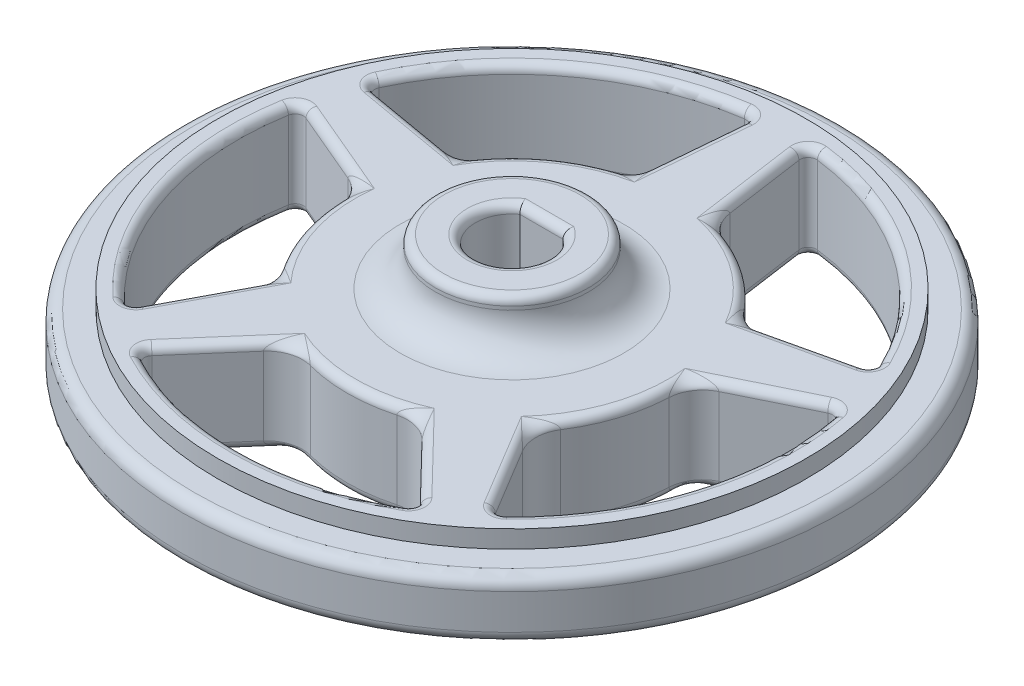
SolidWorks part; units mm, degrees
ref_plane "Front Plane" through (0, 0, 0) normal (0, 0, 1) x (1, 0, 0)
ref_plane "Top Plane" through (0, 0, 0) normal (0, 1, 0) x (1, 0, 0)
ref_plane "Right Plane" through (0, 0, 0) normal (1, 0, 0) x (0, 0, -1)
sketch "Croquis1" plane through (0, 0, 0) normal (0, 1, 0) x (1, 0, 0)
  circle A0 centre (0, 0) radius 6.5
  dimension "D1" = 13
sketch "Sketch1" plane through (0, 0, 0) normal (0, 1, 0) x (1, 0, 0)
  line L0 (4, 0) -> (-4, 0) construction
  line L1 (-3.2894, 13.6081) -> (-2.4528, 23.1705)
  line L2 (0, 0) -> (0, 7.6318) construction
  line L3 (3.2894, 13.6081) -> (1.9176, 23.221)
  line L4 (11.9255, 7.3336) -> (21.2785, 9.4929)
  line L5 (13.9585, 1.0767) -> (22.677, 5.3519)
  line L6 (10.6598, -9.0757) -> (15.6037, -17.3036)
  line L7 (5.3374, -12.9426) -> (12.0976, -19.9133)
  line L8 (-5.3374, -12.9426) -> (-11.6349, -20.1871)
  line L9 (-10.6598, -9.0757) -> (-15.2003, -17.659)
  line L10 (-13.9585, 1.0767) -> (-22.7945, 4.8273)
  line L11 (-11.9255, 7.3336) -> (-21.4919, 8.9994)
  circle A0 centre (0, 0) radius 28
  circle A1 centre (0, 0) radius 25
  circle A2 centre (0, 0) radius 23.3
  circle A3 centre (0, 0) radius 14
  point P11 (0, 0)
  point P34 (0, 0)
  dimension "D1" = 56
  dimension "D4" = 28
  dimension "D5" = 85
  dimension "D6" = 8
  dimension "D2" = 3
  dimension "D3" = 4.7
  dimension "D7" = 5
extrude "Boss-Extrude1" add sketch "Sketch1" along normal mid plane 8 contours A1 A2 region at (-24.2929, 0, 0)
extrude "Boss-Extrude2" add sketch "Sketch1<3>" along normal mid plane 8 contours A3 L11 A2 L10 | A3 | A3 L3 A2 L1 | A3 L5 A2 L4 | A3 L7 A2 L6 | A3 L9 A2 L8 region at (-0.1269, 0, -18.2557) region at (0, 0, 0) region at (-17.4015, 0, -5.5206) region at (17.323, 0, -5.762) region at (-10.6278, 0, 14.8438) region at (10.8331, 0, 14.6946)
sketch "Sketch1<3>" plane through (0, 0, 0) normal (0, 1, 0) x (1, 0, 0) same geometry as "Sketch1"
extrude "Saliente-Extruir1" add sketch "Croquis1" along normal blind 8
sketch "Sketch3" plane through (0, 4, 0) normal (0, 1, 0) x (1, 0, 0)
  line L0 (3.609, -2) -> (-3.609, -2) construction
  line L1 (3.609, 12) -> (-3.609, 12) construction
  line L2 (-1.833, 2.5) -> (1.833, 2.5)
  arc A4 (-1.833, 2.5) -> (1.833, 2.5) centre (0, 0) ccw
  point P8 (0, -2)
  point P11 (0, 12)
  point P17 (0, 0)
  dimension "D1" = 2.5
  dimension "D5" = 6.2
  dimension "D3" = 14
extrude "Cortar-Extruir1" cut sketch "Sketch3" against normal through all both and the other way through all
fillet "Fillet1" radius 0.7 55 edges at (13.1318, -4, 13.1896) (8.7175, -4, 16.428) (-12.9301, -4, 13.3673) (-16.7087, -4, -8.1665) (-18.3765, -4, -2.952) (-13.3148, -4, 4.3262) (-8.4862, -4, 16.5649) (0, -4, 14) (13.3148, -4, 4.3262) (18.3178, -4, -3.2143) (16.602, -4, -8.4132) (8.229, -4, -11.3262) (2.6035, -4, -18.4145) (-2.8711, -4, -18.3893) (-8.229, -4, -11.3262) (8.229, 4, -11.3262) (2.6035, 4, -18.4145) (-2.8711, 4, -18.3893) (-8.229, 4, -11.3262) (-16.7087, 4, -8.1665) (-18.3765, 4, -2.952) (-8.4862, 4, 16.5649) (-12.9301, 4, 13.3673) (-13.3148, 4, 4.3262) (0, 4, 14) (8.7175, 4, 16.428) (13.1318, 4, 13.1896) (13.3148, 4, 4.3262) (18.3178, 4, -3.2143) (16.602, 4, -8.4132) (-13.912, -4, -18.6908) (-21.4919, 0, -8.9994) (-13.912, 4, -18.6908) (-2.4528, 0, -23.1705) (-22.0751, -4, 7.4553) (-15.2003, 0, 17.659) (-22.0751, 4, 7.4553) (-22.7945, 0, -4.8273) (0.2688, -4, 23.2984) (12.0976, 0, 19.9133) (0.2688, 4, 23.2984) (-11.6349, 0, 20.1871) (22.2412, -4, 6.944) (22.677, 0, -5.3519) (22.2412, 4, 6.944) (15.6037, 0, 17.3036) (13.477, -4, -19.0068) (1.9176, 0, -23.221) (13.477, 4, -19.0068) (21.2785, 0, -9.4929) (0, -4, -2.5) (0, -4, 3.1) (0, 8, 6.5) (0, 8, 3.1) (0, 8, -2.5)
fillet "Fillet3" radius 3 31 edges at (-10.5243, 3.681, 9.0606) (-10.5243, -3.681, 9.0606) (-13.7087, 3.8245, -1.2275) (-13.7087, -3.8245, -1.2275) (-5.4036, 3.8245, 12.6584) (-5.4036, -3.8245, 12.6584) (5.365, 3.681, 12.8091) (5.365, -3.681, 12.8091) (10.369, 3.8245, 9.0508) (10.369, -3.8245, 9.0508) (13.84, 3.681, -1.1442) (13.84, -3.681, -1.1442) (11.8121, 3.8245, -7.0647) (11.8121, -3.8245, -7.0647) (3.1886, 3.681, -13.5162) (3.1886, -3.681, -13.5162) (-11.8693, 3.681, -7.2093) (-11.8693, -3.681, -7.2093) (-3.0688, 3.8245, -13.4171) (-3.0688, -3.8245, -13.4171) (-10.6598, 0, 9.0757) (-13.9585, 0, -1.0767) (-5.3374, 0, 12.9426) (5.3374, 0, 12.9426) (10.6598, 0, 9.0757) (13.9585, 0, -1.0767) (11.9255, 0, -7.3336) (3.2894, 0, -13.6081) (-11.9255, 0, -7.3336) (-3.2894, 0, -13.6081) (0, 4, 6.5)
extrude "Boss-Extrude4" add sketch "Sketch1<4>" along normal mid plane 5 contours A0 A1 region at (-27.208, 0, 0)
sketch "Sketch1<4>" plane through (0, 0, 0) normal (0, 1, 0) x (1, 0, 0) same geometry as "Sketch1"
fillet "Fillet4" radius 1 2 edges at (0, -2.5, 28) (0, 2.5, 28)
